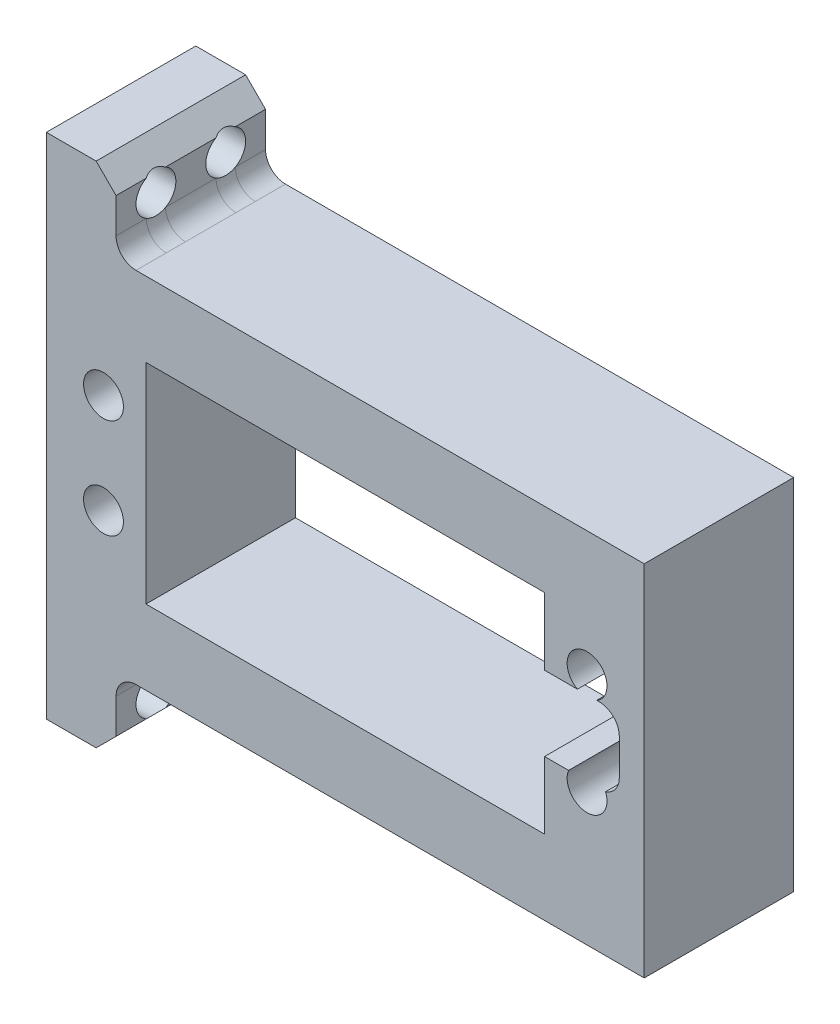
SolidWorks part; units mm, degrees
ref_plane "Front" through (0, 0, 0) normal (0, 0, 1) x (1, 0, 0)
ref_plane "Top" through (0, 0, 0) normal (0, 1, 0) x (1, 0, 0)
ref_plane "Right" through (0, 0, 0) normal (1, 0, 0) x (0, 0, -1)
sketch "Sketch1" plane through (0, 0, 0) normal (0, 0, 1) x (1, 0, 0)
  line L0 (-30, 0) -> (-30, 28.5)
  line L1 (55, 0) -> (-55, 0) construction
  line L4 (-30, 28.5) -> (30, 28.5)
  line L6 (0, -55) -> (0, 55) construction
  line L7 (20, 21) -> (-20, 21)
  line L8 (-20, 21) -> (-20, 0)
  line L9 (-20, 0) -> (-30, 0)
  line L10 (20, 0) -> (30, 0)
  line L11 (20, 21) -> (20, 0)
  line L14 (30, 0) -> (30, 28.5)
  line L17 (-30, 0) -> (-30, 2)
  line L22 (30, 0) -> (30, 2)
  line L23 (-30, 0) -> (-30, -7.5)
  line L24 (-30, 0) -> (30, 0)
  line L26 (-30, -7.5) -> (30, -7.5)
  line L28 (20, 14.25) -> (27.5, 14.25)
  line L29 (20, 14.25) -> (20, 6.75)
  line L30 (20, 6.75) -> (27.5, 6.75)
  line L31 (27.5, 14.25) -> (27.5, 6.75)
  line L32 (30, 0) -> (30, -7.5)
  circle A0 centre (-24.265, 16) radius 2
  circle A1 centre (-24.265, 6) radius 2
  circle A2 centre (24.265, 6) radius 2
  circle A3 centre (24.265, 16) radius 2
  point P16 (0, 21)
  point P17 (0, 28.5)
  point P35 (27.5, 10.5)
  point P36 (20, 10.5)
  dimension "D5" = 4
  dimension "D6" = 7.5
  dimension "D1" = 7.5
  dimension "D2" = 48.53
  dimension "D3" = 10
  dimension "D4" = 20
  dimension "D7" = 10
  dimension "D8" = 21
  dimension "D10" = 7.5
  dimension "D11" = 5
  dimension "D12" = 6
  dimension "D13" = 7.5
extrude "Boss-Extrude1" add sketch "Sketch1" along normal blind 15 contours L0 | L10 L14 L4 L0 L9 L8 L7 L11 A2 A1 A0 A3 | L14 | L10 L24 L9 L26 | L24 L23 L26 L32 region at (-29.3358, 1, 0) region at (0, -3.75, 0)
sketch "Sketch6" plane through (0, 0, 0) normal (1, 0, 0) x (0, 0, -1)
  line L0 (-15, 28.5) -> (0, 28.5) construction
  line L1 (-15, 28.5) -> (0, 28.5)
  line L2 (-15, 28.5) -> (-15, 36)
  line L3 (-15, 36) -> (0, 36)
  line L4 (0, 28.5) -> (0, 36)
  line L5 (-15, -7.5) -> (0, -7.5) construction
  line L6 (-15, 10.5) -> (0, 10.5) construction
  line L7 (-15, -7.5) -> (-15, 28.5) construction
  line L8 (0, 19.8) -> (0, -19.8) construction
  line L9 (-15, -15) -> (0, -15)
  line L10 (0, -7.5) -> (0, -15)
  line L11 (-15, -7.5) -> (0, -7.5)
  line L12 (-15, -7.5) -> (-15, -15)
  line L13 (-4, 32.25) -> (-11, 32.25) construction
  line L14 (-11, 32.25) -> (-15, 32.25) construction
  circle A0 centre (-4, 32.25) radius 2
  circle A1 centre (-11, 32.25) radius 2
  circle A2 centre (-11, -11.25) radius 2
  circle A3 centre (-4, -11.25) radius 2
  point P8 (-7.5, -7.5)
  point P9 (-7.5, 28.5)
  point P28 (-7.5, 32.25)
  point P30 (-7.5, 36)
  dimension "D3" = 4
  dimension "D1" = 15
  dimension "D2" = 7.5
  dimension "D4" = 7
  dimension "D6" = 43.5
extrude "Boss-Extrude2" add sketch "Sketch6" along normal blind 7 from surface starting at face at (-30, 10.5, 7.5)
fillet "Fillet1" radius 2 4 edges at (27.5, 6.75, 7.5) (27.5, 14.25, 7.5) (-23, 28.5, 7.5) (-23, -7.5, 7.5)
sketch "Sketch7" plane through (0, -7.5, 0) normal (0, -1, 0) x (1, 0, 0)
  line L0 (30, 7.5) -> (42, 7.5) construction
  line L1 (30, 15) -> (42, 15)
  line L2 (30, 15) -> (30, 0)
  line L3 (30, 0) -> (42, 0)
  line L4 (42, 15) -> (42, 0)
  line L5 (28.05, 0) -> (-28.05, 0) construction
  circle A2 centre (38, 12.5) radius 1.5
  circle A3 centre (38, 2.5) radius 1.5
  point P9 (34.5175, 11.0643)
  point P12 (0, 0)
  point P14 (0, 0)
  point P15 (36.812, 12.7879)
  dimension "D1" = 3
  dimension "D2" = 12
  dimension "D3" = 10
  dimension "D4" = 4
extrude "Boss-Extrude3" [suppressed] add sketch "Sketch7" along normal blind 5 from surface
chamfer "Chamfer1" distance 2 angle 45 2 edges at (-23, -15, 7.5) (-23, 36, 7.5)
